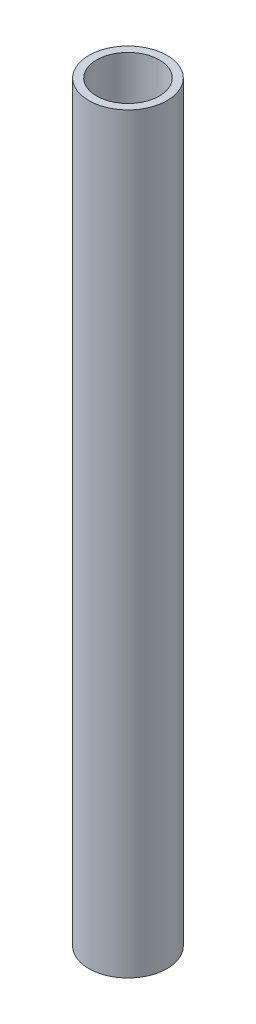
SolidWorks part; units mm, degrees
material "Custom Plastic"
ref_plane "X-Y Datum" through (0, 0, 0) normal (0, 0, 1) x (1, 0, 0)
ref_plane "X-Z Datum" through (0, 0, 0) normal (0, 1, 0) x (1, 0, 0)
ref_plane "Y-Z Datum" through (0, 0, 0) normal (1, 0, 0) x (0, 0, -1)
ref_point "Middle point"
sketch "Sketch2" plane through (0, 0, 0) normal (0, 1, 0) x (1, 0, 0)
  circle A0 centre (0, 0) radius 12.7
  circle A1 centre (0, 0) radius 15.875
  dimension "D1" = 31.75
extrude "Tube Stock - Extrude" add sketch "Sketch2" along normal blind 152.4 and the other way blind 152.4
equation "\"Torsion Tube Stock Outer Diameter\" = 1.25"
equation "\"Torsion Tube Stock Wall Thickness\"= 0.25"
equation "\"D1@Sketch2\"= \"Torsion Tube Stock Outer Diameter\""
equation "\"D2@Sketch2\"= \"Torsion Tube Stock Outer Diameter\" - \"Torsion Tube Stock Wall Thickness\""
equation "\"Torsion Tube Stock Length\"= 12in"
equation "\"D1@Tube Stock - Extrude\"=\"Torsion Tube Stock Length\"/2"
equation "\"D2@Tube Stock - Extrude\"=\"Torsion Tube Stock Length\"/2"
